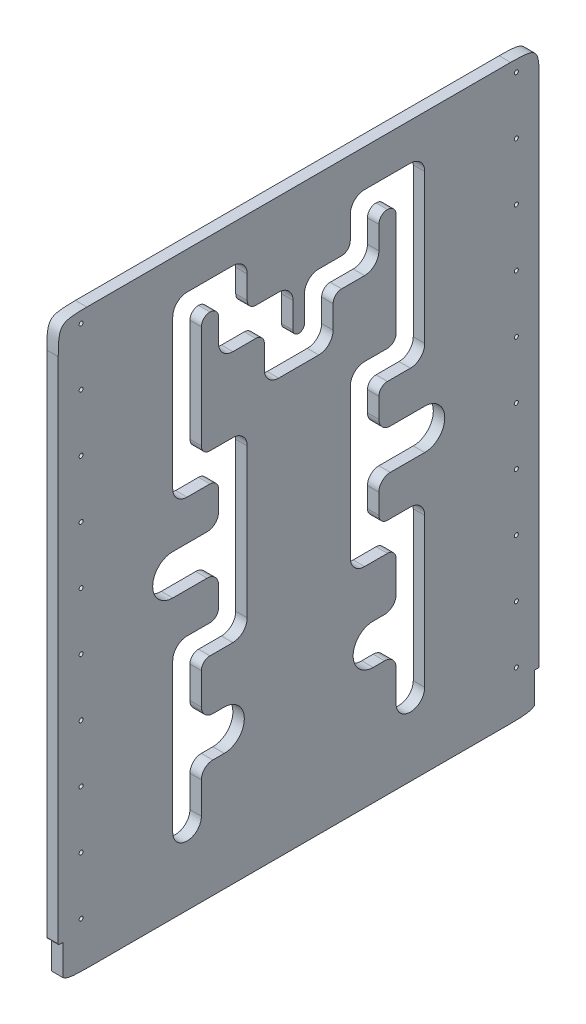
SolidWorks part; units mm, degrees
ref_plane "前视基准面" through (0, 0, 0) normal (0, 0, 1) x (1, 0, 0)
ref_plane "上视基准面" through (0, 0, 0) normal (0, 1, 0) x (1, 0, 0)
ref_plane "右视基准面" through (0, 0, 0) normal (1, 0, 0) x (0, 0, -1)
sketch "草图5" plane through (0, 0, 0) normal (1, 0, 0) x (0, 0, -1)
  line L0 (-120, 240) -> (120, 240)
  line L1 (-120, 240) -> (-120, -240)
  line L2 (120, 240) -> (120, -240)
  line L3 (-120, -240) -> (120, -240)
  line L4 (120, 0) -> (-120, 0) construction
  line L5 (0, 240) -> (0, -240) construction
  line L6 (-120, -240) -> (0, 0) construction
  line L7 (-97.5, -195) -> (-97.5, -65) construction
  line L8 (-97.5, -65) -> (-57.5, -65) construction
  line L9 (-110, -195) -> (-110, -65)
  line L10 (-85, -195) -> (-85, -65)
  line L11 (-57.5, 155) -> (-17.5, 155) construction
  line L12 (-97.5, -52.5) -> (-57.5, -52.5)
  line L13 (-97.5, -77.5) -> (-57.5, -77.5)
  line L14 (-57.5, -65) -> (-57.5, 65) construction
  line L15 (-70, -65) -> (-70, 65)
  line L16 (-45, -65) -> (-45, 65)
  line L17 (-57.5, 65) -> (-97.5, 65) construction
  line L18 (-57.5, 52.5) -> (-97.5, 52.5)
  line L19 (-57.5, 77.5) -> (-97.5, 77.5)
  line L20 (-97.5, 65) -> (-97.5, 195) construction
  line L21 (-110, 65) -> (-110, 195)
  line L22 (-85, 65) -> (-85, 195)
  line L23 (-97.5, 195) -> (-57.5, 195) construction
  line L24 (-97.5, 207.5) -> (-57.5, 207.5)
  line L25 (-97.5, 182.5) -> (-57.5, 182.5)
  line L26 (-57.5, 195) -> (-57.5, 155) construction
  line L27 (-45, 195) -> (-45, 155)
  line L28 (-70, 195) -> (-70, 155)
  line L31 (57.5, 195) -> (57.5, 155) construction
  line L32 (45, 195) -> (45, 155)
  line L33 (70, 195) -> (70, 155)
  line L34 (97.5, 195) -> (57.5, 195) construction
  line L35 (97.5, 207.5) -> (57.5, 207.5)
  line L36 (97.5, 182.5) -> (57.5, 182.5)
  line L37 (17.5, 102.5) -> (-17.5, 102.5)
  line L40 (97.5, 65) -> (97.5, 195) construction
  line L41 (110, 65) -> (110, 195)
  line L42 (85, 65) -> (85, 195)
  line L43 (57.5, 65) -> (97.5, 65) construction
  line L44 (57.5, 52.5) -> (97.5, 52.5)
  line L45 (57.5, 77.5) -> (97.5, 77.5)
  line L46 (57.5, -65) -> (57.5, 65) construction
  line L47 (70, -65) -> (70, 65)
  line L48 (45, -65) -> (45, 65)
  line L49 (97.5, -65) -> (57.5, -65) construction
  line L50 (97.5, -52.5) -> (57.5, -52.5)
  line L51 (97.5, -77.5) -> (57.5, -77.5)
  line L52 (97.5, -195) -> (97.5, -65) construction
  line L53 (110, -195) -> (110, -65)
  line L54 (85, -195) -> (85, -65)
  line L55 (-57.5, 167.5) -> (-17.5, 167.5)
  line L56 (-57.5, 142.5) -> (-17.5, 142.5)
  line L57 (57.5, 155) -> (17.5, 155) construction
  line L58 (57.5, 142.5) -> (17.5, 142.5)
  line L59 (57.5, 167.5) -> (17.5, 167.5)
  line L60 (-17.5, 155) -> (-17.5, 115) construction
  line L61 (-5, 155) -> (-5, 115)
  line L62 (-30, 155) -> (-30, 115)
  line L63 (17.5, 155) -> (17.5, 115) construction
  line L64 (30, 155) -> (30, 115)
  line L65 (5, 155) -> (5, 115)
  line L66 (17.5, 115) -> (-17.5, 115) construction
  line L67 (17.5, 127.5) -> (-17.5, 127.5)
  arc A0 (-110, -195) -> (-85, -195) centre (-97.5, -195) ccw
  arc A1 (-85, -65) -> (-110, -65) centre (-97.5, -65) ccw
  arc A2 (-97.5, -52.5) -> (-97.5, -77.5) centre (-97.5, -65) ccw
  arc A3 (-57.5, -77.5) -> (-57.5, -52.5) centre (-57.5, -65) ccw
  arc A4 (-70, -65) -> (-45, -65) centre (-57.5, -65) ccw
  arc A5 (-45, 65) -> (-70, 65) centre (-57.5, 65) ccw
  arc A6 (-57.5, 52.5) -> (-57.5, 77.5) centre (-57.5, 65) ccw
  arc A7 (-97.5, 77.5) -> (-97.5, 52.5) centre (-97.5, 65) ccw
  arc A8 (-110, 65) -> (-85, 65) centre (-97.5, 65) ccw
  arc A9 (-85, 195) -> (-110, 195) centre (-97.5, 195) ccw
  arc A10 (-97.5, 207.5) -> (-97.5, 182.5) centre (-97.5, 195) ccw
  arc A11 (-57.5, 182.5) -> (-57.5, 207.5) centre (-57.5, 195) ccw
  arc A12 (-45, 195) -> (-70, 195) centre (-57.5, 195) ccw
  arc A13 (-70, 155) -> (-45, 155) centre (-57.5, 155) ccw
  arc A16 (45, 195) -> (70, 195) centre (57.5, 195) cw
  arc A17 (70, 155) -> (45, 155) centre (57.5, 155) cw
  arc A18 (97.5, 207.5) -> (97.5, 182.5) centre (97.5, 195) cw
  arc A19 (57.5, 182.5) -> (57.5, 207.5) centre (57.5, 195) cw
  arc A22 (110, 65) -> (85, 65) centre (97.5, 65) cw
  arc A23 (85, 195) -> (110, 195) centre (97.5, 195) cw
  arc A24 (57.5, 52.5) -> (57.5, 77.5) centre (57.5, 65) cw
  arc A25 (97.5, 77.5) -> (97.5, 52.5) centre (97.5, 65) cw
  arc A26 (70, -65) -> (45, -65) centre (57.5, -65) cw
  arc A27 (45, 65) -> (70, 65) centre (57.5, 65) cw
  arc A28 (97.5, -52.5) -> (97.5, -77.5) centre (97.5, -65) cw
  arc A29 (57.5, -77.5) -> (57.5, -52.5) centre (57.5, -65) cw
  arc A30 (110, -195) -> (85, -195) centre (97.5, -195) cw
  arc A31 (85, -65) -> (110, -65) centre (97.5, -65) cw
  arc A32 (-57.5, 167.5) -> (-57.5, 142.5) centre (-57.5, 155) ccw
  arc A33 (-17.5, 142.5) -> (-17.5, 167.5) centre (-17.5, 155) ccw
  arc A34 (57.5, 142.5) -> (57.5, 167.5) centre (57.5, 155) ccw
  arc A35 (17.5, 167.5) -> (17.5, 142.5) centre (17.5, 155) ccw
  arc A36 (-5, 155) -> (-30, 155) centre (-17.5, 155) ccw
  arc A37 (-30, 115) -> (-5, 115) centre (-17.5, 115) ccw
  arc A38 (30, 155) -> (5, 155) centre (17.5, 155) ccw
  arc A39 (5, 115) -> (30, 115) centre (17.5, 115) ccw
  arc A40 (17.5, 102.5) -> (17.5, 127.5) centre (17.5, 115) ccw
  arc A41 (-17.5, 127.5) -> (-17.5, 102.5) centre (-17.5, 115) ccw
  point P1 (0, 0)
  point P6 (-97.5, -130)
  point P22 (-77.5, -65)
  point P27 (-57.5, 0)
  point P34 (-77.5, 65)
  point P41 (-97.5, 130)
  point P48 (-77.5, 195)
  point P55 (-57.5, 175)
  point P62 (0, 115)
  point P64 (-37.5, 155)
  point P69 (57.5, 175)
  point P76 (77.5, 195)
  point P83 (37.5, 155)
  point P90 (97.5, 130)
  point P97 (77.5, 65)
  point P104 (57.5, 0)
  point P111 (77.5, -65)
  point P118 (97.5, -130)
  point P125 (-17.5, 135)
  point P132 (17.5, 135)
  dimension "D1" = 240
  dimension "D2" = 480
  dimension "D3" = 268.3282
  dimension "D4" = 25
  dimension "D5" = 130
  dimension "D6" = 45
  dimension "D7" = 25
  dimension "D8" = 40
  dimension "D9" = 25
  dimension "D10" = 130
  dimension "D11" = 25
  dimension "D12" = 40
  dimension "D13" = 25
  dimension "D14" = 130
  dimension "D15" = 25
  dimension "D16" = 40
  dimension "D17" = 25
  dimension "D18" = 40
  dimension "D19" = 25
  dimension "D20" = 40
  dimension "D21" = 25
  dimension "D22" = 40
  dimension "D23" = 25
  dimension "D24" = 40
  dimension "D25" = 25
  dimension "D26" = 40
  dimension "D27" = 25
  dimension "D28" = 35
extrude "凸台-拉伸4" add sketch "草图5" along normal blind 10 contours L1 L3 L2 L0 A39 L37 A37 L62 L56 A13 L28 L25 L22 L19 A5 L16 A3 L13 L10 A0 L9 A1 L12 L15 L18 A7 L21 A9 L24 A11 L27 L55 A33 L61 L67 L65 A35 L59 L32 A16 L35 A18 L41 A22 L44 L47 L50 A28 L53 A30 region at (0, -15.3235, 0)
fillet "圆角1" radius 7.5 16 edges at (5, -77.5, 85) (5, -52.5, 70) (5, 52.5, 70) (5, 77.5, 85) (5, 182.5, 85) (5, 182.5, 70) (5, 167.5, 45) (5, 142.5, 30) (5, 142.5, -30) (5, 167.5, -45) (5, 182.5, -70) (5, 182.5, -85) (5, 77.5, -85) (5, 52.5, -70) (5, -77.5, -85) (5, -52.5, -70)
fillet "圆角2" radius 5 2 edges at (5, 127.5, 5) (5, 127.5, -5)
sketch "草图6" plane through (0, 0, 120) normal (0, 0, 1) x (1, 0, 0)
  line L4 (0, 240) -> (0, -240)
  line L5 (0, -240) -> (10, -240)
  line L6 (10, -240) -> (10, 240)
  line L7 (10, 240) -> (0, 240)
  line L8 (0, 240) -> (0, -240)
  line L9 (0, -240) -> (10, -240)
  line L10 (10, -240) -> (10, 240)
  line L11 (10, 240) -> (0, 240)
  dimension "D1" = 0
extrude "凸台-拉伸5" add sketch "草图6" along normal blind 90
sketch "草图7" plane through (0, 0, -120) normal (0, 0, -1) x (-1, 0, 0)
  line L4 (0, -240) -> (0, 240)
  line L5 (0, 240) -> (-10, 240)
  line L6 (-10, 240) -> (-10, -240)
  line L7 (-10, -240) -> (0, -240)
  line L8 (0, -240) -> (0, 240)
  line L9 (0, 240) -> (-10, 240)
  line L10 (-10, 240) -> (-10, -240)
  line L11 (-10, -240) -> (0, -240)
  dimension "D1" = 0
extrude "凸台-拉伸6" add sketch "草图7" along normal blind 90
sketch "草图8" plane through (0, -240, 0) normal (0, -1, 0) x (1, 0, 0)
  line L4 (0, 210) -> (0, -210)
  line L5 (0, -210) -> (10, -210)
  line L6 (10, -210) -> (10, 210)
  line L7 (10, 210) -> (0, 210)
  line L8 (0, 210) -> (0, -210)
  line L9 (0, -210) -> (10, -210)
  line L10 (10, -210) -> (10, 210)
  line L11 (10, 210) -> (0, 210)
  dimension "D1" = 0
extrude "凸台-拉伸7" add sketch "草图8" along normal blind 20
fillet "圆角4" radius 25 4 edges at (5, -260, 210) (5, -260, -210) (5, 240, -210) (5, 240, 210) conic radius 7.5
sketch "草图9" plane through (10, 0, 0) normal (1, 0, 0) x (0, 0, -1)
  line L0 (-1031.227, -220) -> (48968.773, -220) construction
  line L1 (185, -260) -> (-185, -260) construction
  line L2 (-190, -220) -> (190, -220) construction
  line L3 (-110, -130) -> (-210, -130) construction
  line L4 (-190, -220) -> (-190, -170) construction
  line L5 (-110, -195) -> (-110, -65) construction
  line L6 (-210, -235) -> (-210, 215) construction
  line L7 (-190, -1130) -> (-190, 48870) construction
  line L8 (190, -70) -> (190, -120) construction
  line L10 (210, 215) -> (210, -235) construction
  circle A0 centre (-190, -220) radius 1.75
  circle A1 centre (190, -220) radius 1.75
  circle A2 centre (190, -170) radius 1.75
  circle A3 centre (190, -120) radius 1.75
  circle A4 centre (190, -70) radius 1.75
  circle A5 centre (-190, -170) radius 1.75
  circle A6 centre (-190, -120) radius 1.75
  circle A7 centre (-190, -70) radius 1.75
  circle A8 centre (-190, -20) radius 1.75
  circle A9 centre (190, -20) radius 1.75
  circle A10 centre (-190, 30) radius 1.75
  circle A11 centre (190, 30) radius 1.75
  circle A12 centre (-190, 80) radius 1.75
  circle A13 centre (190, 80) radius 1.75
  circle A14 centre (-190, 130) radius 1.75
  circle A15 centre (190, 130) radius 1.75
  circle A16 centre (-190, 180) radius 1.75
  circle A17 centre (190, 180) radius 1.75
  circle A18 centre (-190, 230) radius 1.75
  circle A19 centre (190, 230) radius 1.75
  point P11 (-190, -220)
  dimension "D3" = 3.5
  dimension "D1" = 40
  dimension "D2" = 100
  dimension "D6" = 20
  dimension "D7" = 50
  dimension "D8" = 20
  dimension "D4" = 2
  dimension "D5" = 10
extrude "切除-拉伸1" cut sketch "草图9" against normal blind 20
sketch "草图10" plane through (10, 0, 0) normal (1, 0, 0) x (0, 0, -1)
  line L0 (-210, -260) -> (-206, -260)
  line L1 (-210, -260) -> (-210, -230)
  line L2 (-206, -260) -> (-206, -230)
  line L3 (-210, -230) -> (-206, -230)
  line L4 (-210, 215) -> (-210, -235)
  line L5 (-185, -260) -> (185, -260)
  line L6 (210, -235) -> (210, 215)
  line L7 (185, 240) -> (-185, 240)
  line L8 (-210, 215) -> (-210, -260)
  line L9 (-210, -260) -> (185, -260)
  line L10 (210, -235) -> (210, 215)
  line L11 (185, 240) -> (-185, 240)
  line L12 (-210, -260) -> (-206, -230) construction
  line L13 (-206, -260) -> (-210, -230) construction
  spline S4 degree 2 poles (127.0695, 2745.7701) (-221.0721, -116.5092) (-209.6363, -246.0007) (-209.3495, -249.2485) (-208.7893, -251.4115) (-207.9708, -254.5721) (-206.2916, -256.2612) (-204.6072, -257.9556) (-201.4439, -258.7809) (-199.2778, -259.346) (-196.0153, -259.635) (-66.6846, -271.0912) (2795.878, 77.0323) knots -7.610767 -7.610767 -7.610767 0.25 0.25 0.375 0.375 0.5 0.5 0.625 0.625 0.75 0.75 8.596856 8.596856 8.596856 only from (-210, -235) to (-185, -260)
  spline S5 degree 2 poles (-2795.77, 77.0695) (66.5092, -271.0721) (196.0007, -259.6363) (199.2485, -259.3495) (201.4115, -258.7893) (204.5721, -257.9708) (206.2612, -256.2916) (207.9556, -254.6072) (208.7809, -251.4439) (209.346, -249.2778) (209.635, -246.0153) (221.0912, -116.6846) (-127.0323, 2745.878) knots -7.610767 -7.610767 -7.610767 0.25 0.25 0.375 0.375 0.5 0.5 0.625 0.625 0.75 0.75 8.596856 8.596856 8.596856 only from (185, -260) to (210, -235)
  spline S6 degree 2 poles (-127.0695, -2765.7701) (221.0721, 96.5092) (209.6363, 226.0007) (209.3495, 229.2485) (208.7893, 231.4115) (207.9708, 234.5721) (206.2916, 236.2612) (204.6072, 237.9556) (201.4439, 238.7809) (199.2778, 239.346) (196.0153, 239.635) (66.6846, 251.0912) (-2795.878, -97.0323) knots -7.610767 -7.610767 -7.610767 0.25 0.25 0.375 0.375 0.5 0.5 0.625 0.625 0.75 0.75 8.596856 8.596856 8.596856 only from (210, 215) to (185, 240)
  spline S7 degree 2 poles (2795.7701, -97.0695) (-66.5092, 251.0721) (-196.0007, 239.6363) (-199.2485, 239.3495) (-201.4115, 238.7893) (-204.5721, 237.9708) (-206.2612, 236.2916) (-207.9556, 234.6072) (-208.7809, 231.4439) (-209.346, 229.2778) (-209.635, 226.0153) (-221.0912, 96.6846) (127.0323, -2765.878) knots -7.610767 -7.610767 -7.610767 0.25 0.25 0.375 0.375 0.5 0.5 0.625 0.625 0.75 0.75 8.596856 8.596856 8.596856 only from (-185, 240) to (-210, 215)
  spline S8 degree 2 poles (-210, -235) (-210, -241.8824) (-209.6363, -246.0007) (-209.3495, -249.2485) (-208.7893, -251.4115) (-207.9708, -254.5721) (-206.2916, -256.2612) (-204.6072, -257.9556) (-201.4439, -258.7809) (-199.2778, -259.346) (-196.0153, -259.635) (-191.8948, -260) (-185, -260) knots 0 0 0 0.25 0.25 0.375 0.375 0.5 0.5 0.625 0.625 0.75 0.75 1 1 1
  spline S9 degree 2 poles (185, -260) (191.8824, -260) (196.0007, -259.6363) (199.2485, -259.3495) (201.4115, -258.7893) (204.5721, -257.9708) (206.2612, -256.2916) (207.9556, -254.6072) (208.7809, -251.4439) (209.346, -249.2778) (209.635, -246.0153) (210, -241.8948) (210, -235) knots 0 0 0 0.25 0.25 0.375 0.375 0.5 0.5 0.625 0.625 0.75 0.75 1 1 1
  spline S10 degree 2 poles (210, 215) (210, 221.8824) (209.6363, 226.0007) (209.3495, 229.2485) (208.7893, 231.4115) (207.9708, 234.5721) (206.2916, 236.2612) (204.6072, 237.9556) (201.4439, 238.7809) (199.2778, 239.346) (196.0153, 239.635) (191.8948, 240) (185, 240) knots 0 0 0 0.25 0.25 0.375 0.375 0.5 0.5 0.625 0.625 0.75 0.75 1 1 1
  spline S11 degree 2 poles (-185, 240) (-191.8824, 240) (-196.0007, 239.6363) (-199.2485, 239.3495) (-201.4115, 238.7893) (-204.5721, 237.9708) (-206.2612, 236.2916) (-207.9556, 234.6072) (-208.7809, 231.4439) (-209.346, 229.2778) (-209.635, 226.0153) (-210, 221.8948) (-210, 215) knots 0 0 0 0.25 0.25 0.375 0.375 0.5 0.5 0.625 0.625 0.75 0.75 1 1 1
  point P16 (-208, -245)
  dimension "D2" = 4
  dimension "D3" = 30
  dimension "D1" = 0
extrude "切除-拉伸2" cut sketch "草图10" against normal blind 20 contours L0 L2 L3 L1
fillet "圆角5" radius 1 1 edges at (5, -230, 210)
mirror "镜向2" about plane through (0, 0, 0) normal (0, 0, 1) of "切除-拉伸2"
fillet "圆角6" radius 1 1 edges at (5, -230, -210)
sketch "草图11" plane through (10, 0, 0) normal (1, 0, 0) x (0, 0, -1)
  line L0 (-70, 0) -> (-110, 0) construction
  line L1 (-70, -45) -> (-70, 45) construction
  line L2 (-65, -140) -> (-105, -140) construction
  line L3 (-70, -17.5) -> (-110, -17.5)
  line L4 (-70, 17.5) -> (-110, 17.5)
  line L5 (-65, -157.5) -> (-105, -157.5)
  line L6 (-65, -122.5) -> (-105, -122.5)
  line L7 (110, 0) -> (70, 0) construction
  line L8 (110, -17.5) -> (70, -17.5)
  line L9 (110, 17.5) -> (70, 17.5)
  line L10 (105, -140) -> (65, -140) construction
  line L11 (105, -157.5) -> (65, -157.5)
  line L12 (105, -122.5) -> (65, -122.5)
  line L21 (206, -230) -> (209, -230)
  line L22 (210, -229) -> (210, 215)
  line L23 (185, 240) -> (-185, 240)
  line L24 (-210, 215) -> (-210, -229)
  line L25 (-209, -230) -> (-206, -230)
  line L26 (-206, -230) -> (-206, -256.5387)
  line L27 (-185, -260) -> (185, -260)
  line L28 (206, -230) -> (209, -230)
  line L30 (210, -229) -> (210, 215)
  line L31 (185, 240) -> (-185, 240)
  line L32 (-210, 215) -> (-210, -229)
  line L33 (-209, -230) -> (-206, -230)
  line L34 (-206, -230) -> (-206, -256.5387)
  line L35 (-185, -260) -> (185, -260)
  line L37 (206, -256.5388) -> (206, -230)
  line L38 (206, -256.5388) -> (206, -230)
  line L64 (-5, 132.5) -> (-5, 155)
  line L65 (5, 155) -> (5, 132.5)
  line L66 (37.5, 167.5) -> (17.5, 167.5)
  line L67 (45, 195) -> (45, 175)
  line L68 (97.5, 207.5) -> (57.5, 207.5)
  line L69 (110, 65) -> (110, 195)
  line L70 (77.5, 52.5) -> (97.5, 52.5)
  line L71 (70, -45) -> (70, 45)
  line L72 (97.5, -52.5) -> (77.5, -52.5)
  line L73 (110, -195) -> (110, -65)
  line L74 (85, -85) -> (85, -195)
  line L75 (57.5, -77.5) -> (77.5, -77.5)
  line L76 (45, 65) -> (45, -65)
  line L77 (77.5, 77.5) -> (57.5, 77.5)
  line L78 (85, 175) -> (85, 85)
  line L79 (70, 155) -> (70, 175)
  line L80 (37.5, 142.5) -> (57.5, 142.5)
  line L81 (30, 115) -> (30, 135)
  line L82 (-17.5, 102.5) -> (17.5, 102.5)
  line L83 (-30, 135) -> (-30, 115)
  line L84 (-57.5, 142.5) -> (-37.5, 142.5)
  line L85 (-70, 175) -> (-70, 155)
  line L86 (-85, 85) -> (-85, 175)
  line L87 (-57.5, 77.5) -> (-77.5, 77.5)
  line L88 (-45, -65) -> (-45, 65)
  line L89 (-77.5, -77.5) -> (-57.5, -77.5)
  line L90 (-85, -195) -> (-85, -85)
  line L91 (-110, -65) -> (-110, -195)
  line L92 (-77.5, -52.5) -> (-97.5, -52.5)
  line L93 (-70, 45) -> (-70, -45)
  line L94 (-97.5, 52.5) -> (-77.5, 52.5)
  line L95 (-110, 195) -> (-110, 65)
  line L96 (-57.5, 207.5) -> (-97.5, 207.5)
  line L97 (-45, 175) -> (-45, 195)
  line L98 (-17.5, 167.5) -> (-37.5, 167.5)
  line L99 (-5, 132.5) -> (-5, 155)
  line L100 (5, 155) -> (5, 132.5)
  line L101 (37.5, 167.5) -> (17.5, 167.5)
  line L102 (45, 195) -> (45, 175)
  line L103 (97.5, 207.5) -> (57.5, 207.5)
  line L104 (110, 65) -> (110, 195)
  line L105 (77.5, 52.5) -> (97.5, 52.5)
  line L106 (70, -45) -> (70, 45)
  line L107 (97.5, -52.5) -> (77.5, -52.5)
  line L108 (110, -195) -> (110, -65)
  line L109 (85, -85) -> (85, -195)
  line L110 (57.5, -77.5) -> (77.5, -77.5)
  line L111 (45, 65) -> (45, -65)
  line L112 (77.5, 77.5) -> (57.5, 77.5)
  line L113 (85, 175) -> (85, 85)
  line L114 (70, 155) -> (70, 175)
  line L115 (37.5, 142.5) -> (57.5, 142.5)
  line L116 (30, 115) -> (30, 135)
  line L117 (-17.5, 102.5) -> (17.5, 102.5)
  line L118 (-30, 135) -> (-30, 115)
  line L119 (-57.5, 142.5) -> (-37.5, 142.5)
  line L120 (-70, 175) -> (-70, 155)
  line L121 (-85, 85) -> (-85, 175)
  line L122 (-57.5, 77.5) -> (-77.5, 77.5)
  line L123 (-45, -65) -> (-45, 65)
  line L124 (-77.5, -77.5) -> (-57.5, -77.5)
  line L125 (-85, -195) -> (-85, -85)
  line L126 (-110, -65) -> (-110, -195)
  line L127 (-77.5, -52.5) -> (-97.5, -52.5)
  line L128 (-70, 45) -> (-70, -45)
  line L129 (-97.5, 52.5) -> (-77.5, 52.5)
  line L130 (-110, 195) -> (-110, 65)
  line L131 (-57.5, 207.5) -> (-97.5, 207.5)
  line L132 (-45, 175) -> (-45, 195)
  line L133 (-17.5, 167.5) -> (-37.5, 167.5)
  arc A0 (-70, -17.5) -> (-70, 17.5) centre (-70, 0) ccw
  arc A1 (-110, 17.5) -> (-110, -17.5) centre (-110, 0) ccw
  arc A2 (-65, -157.5) -> (-65, -122.5) centre (-65, -140) ccw
  arc A3 (-105, -122.5) -> (-105, -157.5) centre (-105, -140) ccw
  arc A4 (110, -17.5) -> (110, 17.5) centre (110, 0) ccw
  arc A5 (70, 17.5) -> (70, -17.5) centre (70, 0) ccw
  arc A6 (105, -157.5) -> (105, -122.5) centre (105, -140) ccw
  arc A7 (65, -122.5) -> (65, -157.5) centre (65, -140) ccw
  arc A10 (209, -230) -> (210, -229) centre (209, -229) ccw
  arc A11 (-210, -229) -> (-209, -230) centre (-209, -229) ccw
  arc A13 (-210, -229) -> (-209, -230) centre (-209, -229) ccw
  arc A14 (209, -230) -> (210, -229) centre (209, -229) ccw
  arc A50 (-5, 132.5) -> (0, 127.5) centre (0, 132.5) ccw
  arc A51 (0, 127.5) -> (5, 132.5) centre (0, 132.5) ccw
  arc A52 (17.5, 167.5) -> (5, 155) centre (17.5, 155) ccw
  arc A53 (37.5, 167.5) -> (45, 175) centre (37.5, 175) ccw
  arc A54 (57.5, 207.5) -> (45, 195) centre (57.5, 195) ccw
  arc A55 (110, 195) -> (97.5, 207.5) centre (97.5, 195) ccw
  arc A56 (97.5, 52.5) -> (110, 65) centre (97.5, 65) ccw
  arc A57 (77.5, 52.5) -> (70, 45) centre (77.5, 45) ccw
  arc A58 (70, -45) -> (77.5, -52.5) centre (77.5, -45) ccw
  arc A59 (110, -65) -> (97.5, -52.5) centre (97.5, -65) ccw
  arc A60 (85, -195) -> (110, -195) centre (97.5, -195) ccw
  arc A61 (85, -85) -> (77.5, -77.5) centre (77.5, -85) ccw
  arc A62 (45, -65) -> (57.5, -77.5) centre (57.5, -65) ccw
  arc A63 (57.5, 77.5) -> (45, 65) centre (57.5, 65) ccw
  arc A64 (77.5, 77.5) -> (85, 85) centre (77.5, 85) ccw
  arc A65 (85, 175) -> (77.5, 182.5) centre (77.5, 175) ccw
  arc A66 (77.5, 182.5) -> (70, 175) centre (77.5, 175) ccw
  arc A67 (57.5, 142.5) -> (70, 155) centre (57.5, 155) ccw
  arc A68 (37.5, 142.5) -> (30, 135) centre (37.5, 135) ccw
  arc A69 (17.5, 102.5) -> (30, 115) centre (17.5, 115) ccw
  arc A70 (-30, 115) -> (-17.5, 102.5) centre (-17.5, 115) ccw
  arc A71 (-30, 135) -> (-37.5, 142.5) centre (-37.5, 135) ccw
  arc A72 (-70, 155) -> (-57.5, 142.5) centre (-57.5, 155) ccw
  arc A73 (-70, 175) -> (-77.5, 182.5) centre (-77.5, 175) ccw
  arc A74 (-77.5, 182.5) -> (-85, 175) centre (-77.5, 175) ccw
  arc A75 (-85, 85) -> (-77.5, 77.5) centre (-77.5, 85) ccw
  arc A76 (-45, 65) -> (-57.5, 77.5) centre (-57.5, 65) ccw
  arc A77 (-57.5, -77.5) -> (-45, -65) centre (-57.5, -65) ccw
  arc A78 (-77.5, -77.5) -> (-85, -85) centre (-77.5, -85) ccw
  arc A79 (-110, -195) -> (-85, -195) centre (-97.5, -195) ccw
  arc A80 (-97.5, -52.5) -> (-110, -65) centre (-97.5, -65) ccw
  arc A81 (-77.5, -52.5) -> (-70, -45) centre (-77.5, -45) ccw
  arc A82 (-70, 45) -> (-77.5, 52.5) centre (-77.5, 45) ccw
  arc A83 (-110, 65) -> (-97.5, 52.5) centre (-97.5, 65) ccw
  arc A84 (-97.5, 207.5) -> (-110, 195) centre (-97.5, 195) ccw
  arc A85 (-45, 195) -> (-57.5, 207.5) centre (-57.5, 195) ccw
  arc A86 (-45, 175) -> (-37.5, 167.5) centre (-37.5, 175) ccw
  arc A87 (-5, 155) -> (-17.5, 167.5) centre (-17.5, 155) ccw
  arc A88 (-5, 132.5) -> (0, 127.5) centre (0, 132.5) ccw
  arc A89 (0, 127.5) -> (5, 132.5) centre (0, 132.5) ccw
  arc A90 (17.5, 167.5) -> (5, 155) centre (17.5, 155) ccw
  arc A91 (37.5, 167.5) -> (45, 175) centre (37.5, 175) ccw
  arc A92 (57.5, 207.5) -> (45, 195) centre (57.5, 195) ccw
  arc A93 (110, 195) -> (97.5, 207.5) centre (97.5, 195) ccw
  arc A94 (97.5, 52.5) -> (110, 65) centre (97.5, 65) ccw
  arc A95 (77.5, 52.5) -> (70, 45) centre (77.5, 45) ccw
  arc A96 (70, -45) -> (77.5, -52.5) centre (77.5, -45) ccw
  arc A97 (110, -65) -> (97.5, -52.5) centre (97.5, -65) ccw
  arc A98 (85, -195) -> (110, -195) centre (97.5, -195) ccw
  arc A99 (85, -85) -> (77.5, -77.5) centre (77.5, -85) ccw
  arc A100 (45, -65) -> (57.5, -77.5) centre (57.5, -65) ccw
  arc A101 (57.5, 77.5) -> (45, 65) centre (57.5, 65) ccw
  arc A102 (77.5, 77.5) -> (85, 85) centre (77.5, 85) ccw
  arc A103 (85, 175) -> (77.5, 182.5) centre (77.5, 175) ccw
  arc A104 (77.5, 182.5) -> (70, 175) centre (77.5, 175) ccw
  arc A105 (57.5, 142.5) -> (70, 155) centre (57.5, 155) ccw
  arc A106 (37.5, 142.5) -> (30, 135) centre (37.5, 135) ccw
  arc A107 (17.5, 102.5) -> (30, 115) centre (17.5, 115) ccw
  arc A108 (-30, 115) -> (-17.5, 102.5) centre (-17.5, 115) ccw
  arc A109 (-30, 135) -> (-37.5, 142.5) centre (-37.5, 135) ccw
  arc A110 (-70, 155) -> (-57.5, 142.5) centre (-57.5, 155) ccw
  arc A111 (-70, 175) -> (-77.5, 182.5) centre (-77.5, 175) ccw
  arc A112 (-77.5, 182.5) -> (-85, 175) centre (-77.5, 175) ccw
  arc A113 (-85, 85) -> (-77.5, 77.5) centre (-77.5, 85) ccw
  arc A114 (-45, 65) -> (-57.5, 77.5) centre (-57.5, 65) ccw
  arc A115 (-57.5, -77.5) -> (-45, -65) centre (-57.5, -65) ccw
  arc A116 (-77.5, -77.5) -> (-85, -85) centre (-77.5, -85) ccw
  arc A117 (-110, -195) -> (-85, -195) centre (-97.5, -195) ccw
  arc A118 (-97.5, -52.5) -> (-110, -65) centre (-97.5, -65) ccw
  arc A119 (-77.5, -52.5) -> (-70, -45) centre (-77.5, -45) ccw
  arc A120 (-70, 45) -> (-77.5, 52.5) centre (-77.5, 45) ccw
  arc A121 (-110, 65) -> (-97.5, 52.5) centre (-97.5, 65) ccw
  arc A122 (-97.5, 207.5) -> (-110, 195) centre (-97.5, 195) ccw
  arc A123 (-45, 195) -> (-57.5, 207.5) centre (-57.5, 195) ccw
  arc A124 (-45, 175) -> (-37.5, 167.5) centre (-37.5, 175) ccw
  arc A125 (-5, 155) -> (-17.5, 167.5) centre (-17.5, 155) ccw
  spline S4 degree 2 poles (-7.3144, -1773.0557) (218.8903, 121.2149) (209.6363, 226.0007) (209.3495, 229.2485) (208.7893, 231.4115) (207.9708, 234.5721) (206.2916, 236.2612) (204.6072, 237.9556) (201.4439, 238.7809) (199.2778, 239.346) (196.0153, 239.635) (91.3594, 248.9055) (-1803.0796, 22.7149) knots -6.111008 -6.111008 -6.111008 0.25 0.25 0.375 0.375 0.5 0.5 0.625 0.625 0.75 0.75 7.099765 7.099765 7.099765 only from (210, 215) to (185, 240)
  spline S5 degree 2 poles (1803.0557, 22.6856) (-91.2149, 248.8903) (-196.0007, 239.6363) (-199.2485, 239.3495) (-201.4115, 238.7893) (-204.5721, 237.9708) (-206.2612, 236.2916) (-207.9556, 234.6072) (-208.7809, 231.4439) (-209.346, 229.2778) (-209.635, 226.0153) (-218.9055, 121.3594) (7.2851, -1773.0796) knots -6.111008 -6.111008 -6.111008 0.25 0.25 0.375 0.375 0.5 0.5 0.625 0.625 0.75 0.75 7.099765 7.099765 7.099765 only from (-185, 240) to (-210, 215)
  spline S6 degree 2 poles (1430.8208, 890.6611) (-313.5208, -229.5434) (-201.4441, -258.7811) (-199.2779, -259.3462) (-196.0154, -259.6352) (-91.359, -268.904) (1803.0724, -42.6847) knots -3.803682 -3.803682 -3.803682 0.625 0.625 0.75 0.75 7.099726 7.099726 7.099726 only from (-206, -256.5387) to (-185, -260)
  spline S7 degree 2 poles (-1803.0541, -42.659) (91.2144, -268.8891) (196.0008, -259.6364) (199.2486, -259.3497) (201.4117, -258.7895) (313.7653, -229.6951) (-1433.3078, 887.0517) knots -6.110982 -6.110982 -6.110982 0.25 0.25 0.375 0.375 4.818487 4.818487 4.818487 only from (185, -260) to (206, -256.5388)
  spline S8 degree 2 poles (210, 215) (210, 221.8824) (209.6363, 226.0007) (209.3495, 229.2485) (208.7893, 231.4115) (207.9708, 234.5721) (206.2916, 236.2612) (204.6072, 237.9556) (201.4439, 238.7809) (199.2778, 239.346) (196.0153, 239.635) (191.8948, 240) (185, 240) knots 0 0 0 0.25 0.25 0.375 0.375 0.5 0.5 0.625 0.625 0.75 0.75 1 1 1
  spline S9 degree 2 poles (-185, 240) (-191.8824, 240) (-196.0007, 239.6363) (-199.2485, 239.3495) (-201.4115, 238.7893) (-204.5721, 237.9708) (-206.2612, 236.2916) (-207.9556, 234.6072) (-208.7809, 231.4439) (-209.346, 229.2778) (-209.635, 226.0153) (-210, 221.8948) (-210, 215) knots 0 0 0 0.25 0.25 0.375 0.375 0.5 0.5 0.625 0.625 0.75 0.75 1 1 1
  spline S10 degree 2 poles (-206, -256.5387) (-204.3431, -258.0249) (-201.4441, -258.7811) (-199.2779, -259.3462) (-196.0154, -259.6352) (-191.8949, -260.0001) (-185, -260) knots 0.510448 0.510448 0.510448 0.625 0.625 0.75 0.75 1 1 1
  spline S11 degree 2 poles (185, -260) (191.8825, -260.0001) (196.0008, -259.6364) (199.2486, -259.3497) (201.4117, -258.7895) (204.3354, -258.0324) (206, -256.5388) knots 0 0 0 0.25 0.25 0.375 0.375 0.490631 0.490631 0.490631
  point P7 (-90, 0)
  point P12 (-85, -140)
  point P19 (90, 0)
  point P26 (85, -140)
  dimension "D1" = 35
  dimension "D2" = 40
  dimension "D4" = 0
  dimension "D3" = 0
extrude "切除-拉伸3" cut sketch "草图11" against normal blind 10 contours L4 A1 L3 L128 | L8 A4 L9 L106 | L12 A7 L11 L109 | L5 A2 L6 L125 region at (10, 0, 97.0142) region at (10, -140, 67.9017) region at (10, 0, -97.0142) region at (10, -140, -67.9017)
fillet "圆角7" radius 10 8 edges at (5, -157.5, -85) (5, -122.5, -85) (5, -157.5, 85) (5, -122.5, 85) (5, -17.5, -70) (5, 17.5, -70) (5, -17.5, 70) (5, 17.5, 70)
